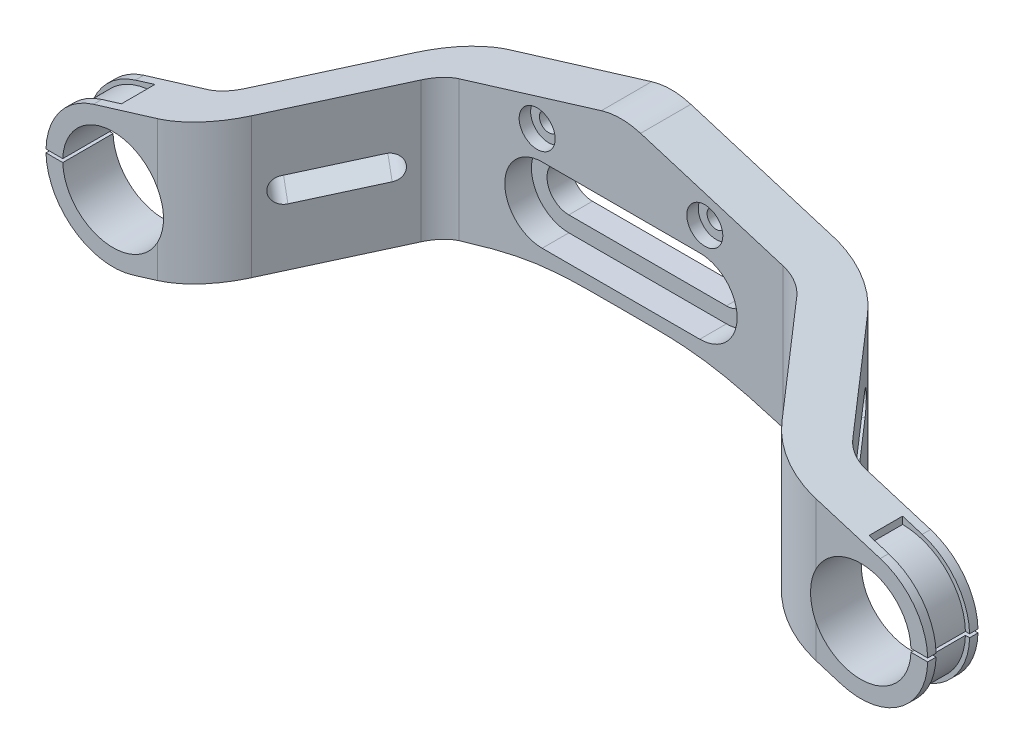
SolidWorks part; units mm, degrees
ref_plane "Front" through (0, 0, 0) normal (0, 0, 1) x (1, 0, 0)
ref_plane "Top" through (0, 0, 0) normal (0, 1, 0) x (1, 0, 0)
ref_plane "Right" through (0, 0, 0) normal (1, 0, 0) x (0, 0, -1)
sketch "Sketch1" plane through (0, 0, 0) normal (0, 1, 0) x (1, 0, 0)
  line L0 (0, 0) -> (-96.6846, 0)
  line L1 (-134.9868, -17.8606) -> (-181.1332, -72.8558)
  line L2 (-196.4541, -80) -> (-280, -80)
  arc A0 (-96.6846, 0) -> (-134.9868, -17.8606) centre (-96.6846, -50) ccw
  arc A1 (-181.1332, -72.8558) -> (-196.4541, -80) centre (-196.4541, -60) cw
  point P9 (-120, 0)
  dimension "D1" = 120
  dimension "D4" = 50
  dimension "D5" = 20
  dimension "D2" = 80
  dimension "D3" = 280
  dimension "D6" = 50
extrude "Extrude-Thin1" add sketch "Sketch1" against normal blind 150 thin thin type one direction reverse wall 30
sketch "Sketch2" plane through (0, 0, 0) normal (0, 0, 1) x (1, 0, 0)
  line L0 (0, 0) -> (-234.6765, -71.7478)
  line L2 (0, -150) -> (0, 0) construction
  line L3 (0, -100) -> (0, 0)
  line L4 (0, 0) -> (-96.6846, 0) construction
  line L5 (-196.4541, -150) -> (-280, -150) construction
  line L6 (-211.2868, -148.2522) -> (-95, -112.6998)
  line L7 (44.3467, -100) -> (-44.3467, -100) construction
  line L8 (-55.2954, -100.5608) -> (-134.1815, -124.6787) construction
  arc A0 (-234.6765, -71.7478) -> (-211.2868, -148.2522) centre (-222.9816, -110) ccw
  spline S0 degree 3 poles (-95, -112.6998) (-51.5325, -99.4104) (-36.9555, -100) (0, -100) knots 0 0 0 0 1 1 1 1
  dimension "D2" = 40
  dimension "D1" = 17
  dimension "D3" = 100
  dimension "D4" = 95
extrude "Cut-Extrude1" cut sketch "Sketch2" along normal through all flip side to cut
sketch "Sketch3" plane through (0, 0, 110) normal (0, 0, 1) x (1, 0, 0)
  circle A0 centre (-222.9816, -110) radius 30
  dimension "D1" = 60
extrude "Cut-Extrude2" cut sketch "Sketch3" against normal through all
sketch "Sketch4" plane through (0, 0, 110) normal (0, 0, 1) x (1, 0, 0)
  line L0 (-222.9816, -68.1723) -> (-222.9816, -72.5)
  line L1 (-196.4541, -60.0621) -> (-234.6765, -71.7478) construction
  line L2 (-234.6765, -71.7478) -> (-222.9816, -68.1723)
  line L3 (-222.9816, -147.5) -> (-222.9816, -150)
  arc A0 (-234.6765, -71.7478) -> (-211.2868, -148.2522) centre (-222.9816, -110) ccw construction
  arc A1 (-234.6765, -71.7478) -> (-222.9816, -150) centre (-222.9816, -110) ccw
  arc A2 (-222.9816, -72.5) -> (-222.9816, -147.5) centre (-222.9816, -110) ccw
  dimension "D1" = 2.5
extrude "Cut-Extrude3" cut sketch "Sketch4" against normal mid plane 20 from offset 15 offset against normal yes
sketch "Sketch5" plane through (0, 0, 110) normal (0, 0, 1) x (1, 0, 0)
  line L5 (-322.9816, -109) -> (-222.9816, -109)
  line L6 (-322.9816, -109) -> (-322.9816, -111)
  line L7 (-322.9816, -111) -> (-222.9816, -111)
  line L8 (-222.9816, -109) -> (-222.9816, -111)
  dimension "D1" = 2
  dimension "D2" = 100
extrude "Cut-Extrude4" cut sketch "Sketch5" against normal through all
hole_wizard "CBORE SLOT for M24 Hex Head Bolt1" positions "Sketch6" profile "Sketch7" size "M24" standard "ANSI Metric" slot yes end condition through all
sketch "Sketch6" plane through (0, 0, 30) normal (0, 0, 1) x (1, 0, 0)
  line L0 (0, -100) -> (0, 0) construction
  line L1 (-60, -70) -> (60, -70) construction
  point P10 (0, -70)
  dimension "D1" = 120
  dimension "D2" = 30
sketch "Sketch7" plane through (0, -70, 30) normal (1, 0, 0) x (0, -1, 0)
  line L0 (0, 0) -> (0, 30)
  line L1 (0, 30) -> (13, 30)
  line L3 (13, 30) -> (13, 15.9)
  line L4 (13, 15.9) -> (22.285, 15.9)
  line L5 (22.285, 15.9) -> (22.285, 0)
  line L7 (22.285, 0) -> (0, 0)
  line L11 (0, -6.35) -> (0, 107.95) construction
  dimension "Thru Hole Dia." = 26
  dimension "Thru Hole Depth" = 30
  dimension "C'Bore Dia." = 44.57
  dimension "C'Bore Depth" = 15.9
hole_wizard "CBORE for M10 Hex Head Bolt1" positions "Sketch9" profile "Sketch10" counterbore size "M10" standard "ANSI Metric" end condition through all
sketch "Sketch9" plane through (0, 0, 30) normal (0, 0, 1) x (1, 0, 0)
  line L0 (0, -47.715) -> (0, 0) construction
  point P0 (-50, -32)
  dimension "D1" = 50
  dimension "D2" = 32
sketch "Sketch10" plane through (-50, -32, 30) normal (1, 0, 0) x (0, -1, 0)
  line L0 (0, 0) -> (0, 30)
  line L1 (0, 30) -> (5.5, 30)
  line L3 (5.5, 30) -> (5.5, 6.85)
  line L4 (5.5, 6.85) -> (10.74, 6.85)
  line L5 (10.74, 6.85) -> (10.74, 0)
  line L7 (10.74, 0) -> (0, 0)
  line L11 (0, -6.35) -> (0, 107.95) construction
  dimension "Thru Hole Dia." = 11
  dimension "Thru Hole Depth" = 30
  dimension "C'Bore Dia." = 21.48
  dimension "C'Bore Depth" = 6.85
sketch "Sketch11" plane through (-47.4376, 0, -39.8048) normal (0.766, 0, 0.6428) x (0.6428, 0, -0.766)
  line L0 (-158.3426, -87.4483) -> (-114.1871, -78.7708) construction
  line L1 (-159.7888, -80.089) -> (-115.6334, -71.4116)
  line L2 (-156.8963, -94.8075) -> (-112.7409, -86.1301)
  line L3 (-100.4499, -34.2435) -> (-172.2409, -48.3519) construction
  line L4 (-114.1871, -78.7708) -> (-100.4499, -76.0712) construction
  line L5 (-100.4499, -117.8989) -> (-100.4499, -34.2435) construction
  arc A0 (-159.7888, -80.089) -> (-156.8963, -94.8075) centre (-158.3426, -87.4483) ccw
  arc A1 (-112.7409, -86.1301) -> (-115.6334, -71.4116) centre (-114.1871, -78.7708) ccw
  point P2 (-136.2649, -83.1095)
  dimension "D1" = 45
  dimension "D2" = 15
  dimension "D3" = 36.5
extrude "Cut-Extrude5" cut sketch "Sketch11" against normal through all
mirror "Mirror1" about plane through (0, -150, 0) normal (-1, 0, 0) of bodies 108
fillet "Fillet1" radius 40 1 edges at (0, 0, 15)
